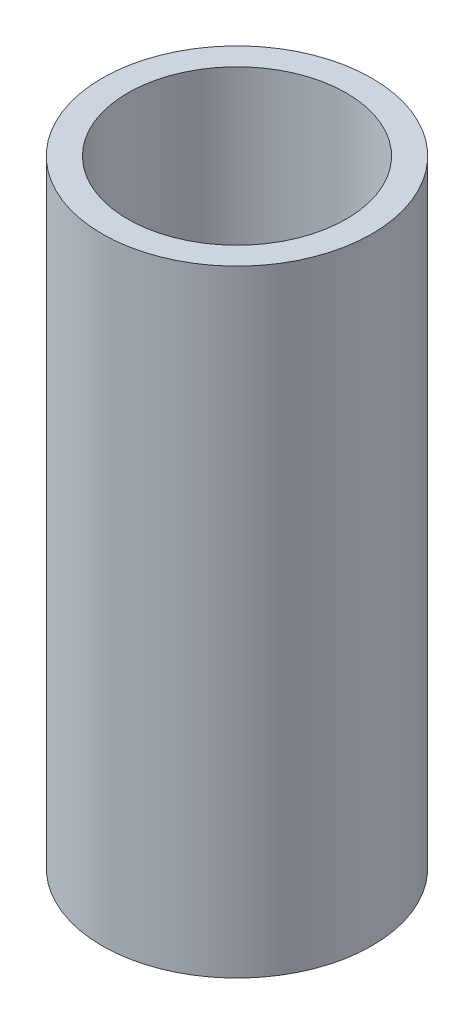
SolidWorks part; units mm, degrees
ref_plane "Front Plane" through (0, 0, 0) normal (0, 0, 1) x (1, 0, 0)
ref_plane "Top Plane" through (0, 0, 0) normal (0, 1, 0) x (1, 0, 0)
ref_plane "Right Plane" through (0, 0, 0) normal (1, 0, 0) x (0, 0, -1)
sketch "Sketch1" plane through (0, 0, 0) normal (0, 1, 0) x (1, 0, 0)
  circle A0 centre (0, 0) radius 25
  dimension "SLEEVE_OD" = 50
extrude "Boss-Extrude1" add sketch "Sketch1" along normal blind 114.2711
sketch "Sketch2" plane through (0, 0, 0) normal (0, 1, 0) x (1, 0, 0)
  circle A0 centre (0, 0) radius 20.2578
  dimension "BORE_D" = 40.5156
extrude "Cut-Extrude1" cut sketch "Sketch2" along normal through all
chamfer "Chamfer1" distance 3.2548 angle 45 rebuild error yes
